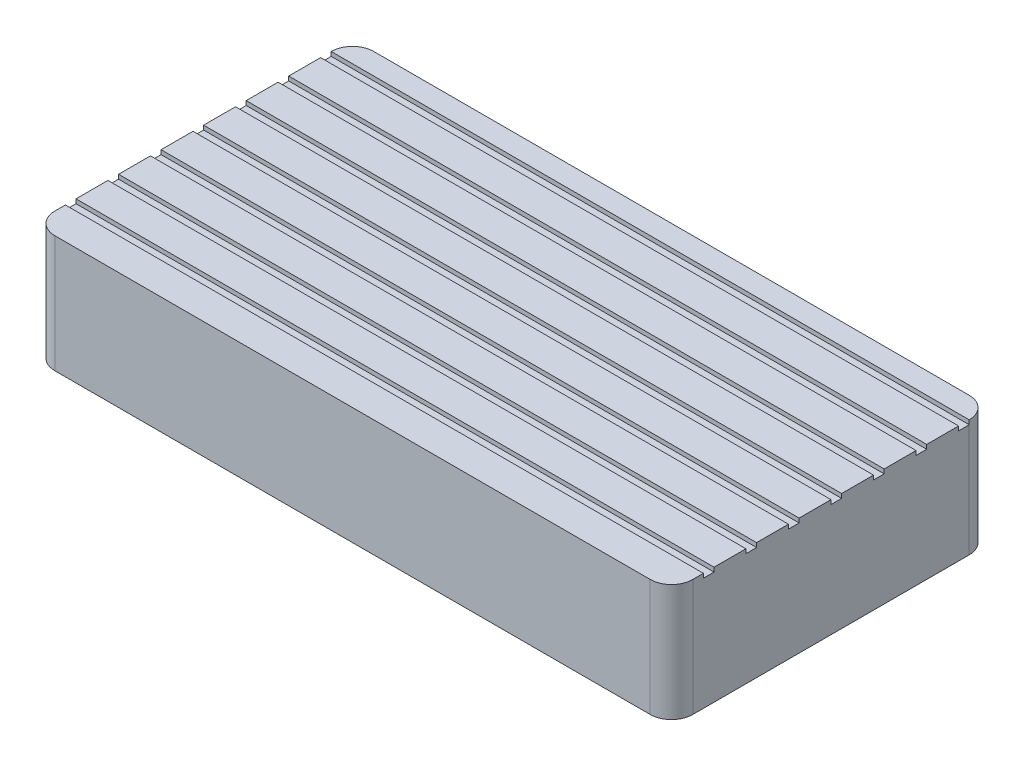
SolidWorks part; units mm, degrees
material "Copper"
ref_plane "Front Plane" through (0, 0, 0) normal (0, 0, 1) x (1, 0, 0)
ref_plane "Top Plane" through (0, 0, 0) normal (0, 1, 0) x (1, 0, 0)
ref_plane "Right Plane" through (0, 0, 0) normal (1, 0, 0) x (0, 0, -1)
sketch "Sketch1" plane through (0, 0, 0) normal (0, 1, 0) x (1, 0, 0)
  line L0 (-15, 0) -> (0, 0) construction
  line L1 (-15, -7.5) -> (15, -7.5)
  line L2 (-15, -7.5) -> (-15, 7.5)
  line L3 (-15, 7.5) -> (15, 7.5)
  line L4 (15, -7.5) -> (15, 7.5)
  line L5 (0, 0) -> (0, -7.5) construction
  dimension "D1" = 15
  dimension "D2" = 30
extrude "Boss-Extrude1" add sketch "Sketch1" along normal blind 5.5
sketch "Sketch2" plane through (0, 0, 0) normal (1, 0, 0) x (0, 0, -1)
  line L0 (-7.5, 5.5) -> (7.5, 5.5) construction
  line L1 (-6, 5.5) -> (-5.5, 5.5)
  line L2 (-6, 5.5) -> (-6, 5.3)
  line L3 (-6, 5.3) -> (-5.5, 5.3)
  line L4 (-5.5, 5.5) -> (-5.5, 5.3)
  line L5 (-7.5, 5.5) -> (-7.5, 0) construction
  line L6 (-3.5, 5.5) -> (-3.5, 5.3)
  line L7 (-4, 5.5) -> (-3.5, 5.5)
  line L8 (-4, 5.5) -> (-4, 5.3)
  line L9 (-4, 5.3) -> (-3.5, 5.3)
  line L10 (-1.5, 5.5) -> (-1.5, 5.3)
  line L11 (-2, 5.5) -> (-1.5, 5.5)
  line L12 (-2, 5.5) -> (-2, 5.3)
  line L13 (-2, 5.3) -> (-1.5, 5.3)
  line L14 (0.5, 5.5) -> (0.5, 5.3)
  line L15 (0, 5.5) -> (0.5, 5.5)
  line L16 (0, 5.5) -> (0, 5.3)
  line L17 (0, 5.3) -> (0.5, 5.3)
  line L18 (2.5, 5.5) -> (2.5, 5.3)
  line L19 (2, 5.5) -> (2.5, 5.5)
  line L20 (2, 5.5) -> (2, 5.3)
  line L21 (2, 5.3) -> (2.5, 5.3)
  line L22 (4.5, 5.5) -> (4.5, 5.3)
  line L23 (4, 5.5) -> (4.5, 5.5)
  line L24 (4, 5.5) -> (4, 5.3)
  line L25 (4, 5.3) -> (4.5, 5.3)
  line L26 (6.5, 5.5) -> (6.5, 5.3)
  line L27 (6, 5.5) -> (6.5, 5.5)
  line L28 (6, 5.5) -> (6, 5.3)
  line L29 (6, 5.3) -> (6.5, 5.3)
  dimension "D1" = 0.2
  dimension "D2" = 0.5
  dimension "D3" = 1.5
  dimension "D5" = 1.5
  dimension "D4" = 7
extrude "Cut-Extrude2" cut sketch "Sketch2" against normal through all both and the other way through all
ref_plane "Plane1" through (0, 0, 4) normal (0, 0, 1) x (1, 0, 0)
sketch "Sketch8" plane through (0, 0, 4) normal (0, 0, 1) x (1, 0, 0)
  line L0 (10.25, 0) -> (10.25, 3)
  line L1 (-15, 0) -> (15, 0) construction
  line L2 (10.25, 3) -> (9, 3.7217)
  line L3 (9, 3.7217) -> (9, 0)
  line L4 (9, 0) -> (10.25, 0)
  line L5 (0, 0) -> (0, 7.2512) construction
  line L6 (9, 0) -> (9, 5.5) construction
  line L7 (-15, 5.5) -> (15, 5.5) construction
  dimension "D1" = 18
  dimension "D2" = 2.5
  dimension "D3" = 3
  dimension "D4" = 60
revolve "Cut-Revolve1" cut sketch "Sketch8" angle 360 about L6
mirror "Mirror1" about plane through (0, 0, 0) normal (0, 0, 1) of "Cut-Revolve1"
mirror "Mirror2" about plane through (0, 0, 0) normal (1, 0, 0) of "Mirror1"
sketch "Sketch5" plane through (-15, 0, 0) normal (1, 0, 0) x (0, 0, -1)
  line L0 (-7.5, 0) -> (7.5, 0) construction
  line L1 (4.1, 0) -> (-5.1, 0)
  line L2 (4.1, 0) -> (4.1, 5.5)
  line L3 (4.1, 5.5) -> (-5.1, 5.5)
  line L4 (-5.1, 0) -> (-5.1, 5.5)
  line L5 (-3.5, 5.5) -> (-2, 5.5) construction
  line L6 (7.5, 0) -> (-7.5, 0) construction
  line L7 (-0.5, 0) -> (-0.5, 5.5) construction
  dimension "D1" = 9.2
  dimension "D2" = 0.5
extrude "Cut-Extrude4" [suppressed] cut sketch "Sketch5" along normal blind 1.6
sketch "Sketch9" plane through (0, 0, 0) normal (0, 0, 1) x (1, 0, 0)
  line L0 (-15, 2.5) -> (-7.6783, 2.5)
  line L1 (-15, 5.5) -> (-15, 0) construction
  line L2 (-7.6783, 2.5) -> (-8.4, 3.75)
  line L3 (-8.4, 3.75) -> (-15, 3.75)
  line L4 (-15, 3.75) -> (-15, 2.5)
  line L5 (-15, 2.5) -> (-16.9854, 2.5) construction
  line L6 (15, 0) -> (-15, 0) construction
  dimension "D1" = 2.5
  dimension "D2" = 6.6
  dimension "D3" = 60
  dimension "D4" = 2.5
revolve "Cut-Revolve2" cut sketch "Sketch9" angle 360 about L5
sketch "Sketch7" plane through (0, 0, 0) normal (0, -1, 0) x (1, 0, 0)
  line L0 (17.59, 0) -> (0, 0) construction
  circle A0 centre (17.59, 0) radius 6.5
  dimension "D1" = 13
  dimension "D2" = 17.59
extrude "Cut-Extrude6" [suppressed] cut sketch "Sketch7" against normal blind 1.75
fillet "Fillet1" radius 1 4 edges at (-15, 2.75, 7.5) (-15, 2.75, -7.5) (15, 2.75, -7.5) (15, 2.75, 7.5)
